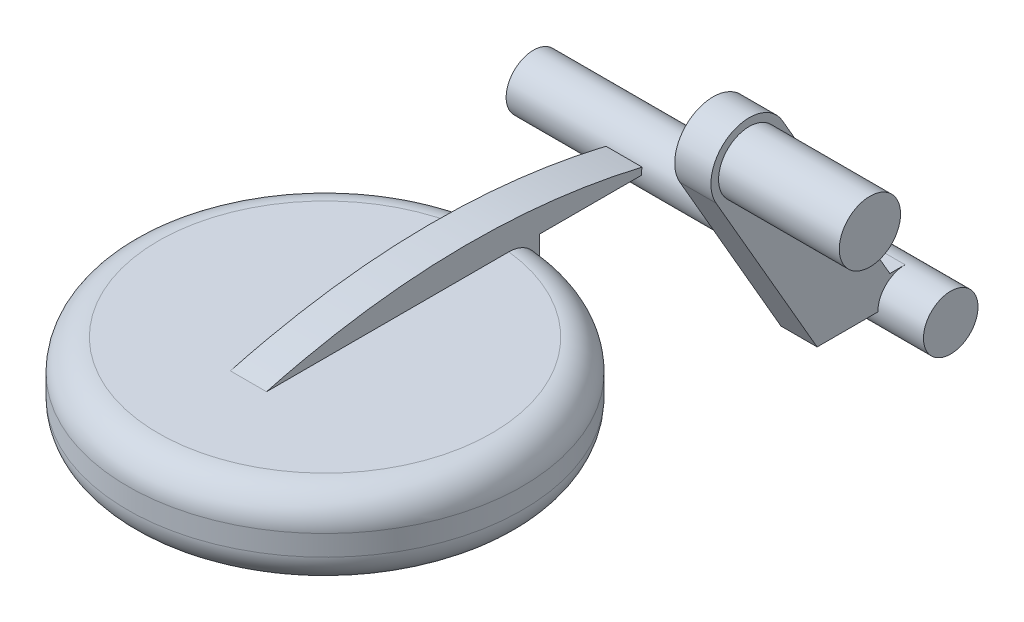
SolidWorks part; units mm, degrees
material "6061 Alloy"
ref_plane "Front Plane" through (0, 0, 0) normal (0, 0, 1) x (1, 0, 0)
ref_plane "Top Plane" through (0, 0, 0) normal (0, 1, 0) x (1, 0, 0)
ref_plane "Right Plane" through (0, 0, 0) normal (1, 0, 0) x (0, 0, -1)
sketch "Sketch1" plane through (0, 0, 0) normal (1, 0, 0) x (0, 0, -1)
  circle A0 centre (0, 0) radius 2.2606
  dimension "D1" = 4.5212
extrude "Boss-Extrude1" add sketch "Sketch1" along normal blind 34.5948
ref_plane "Plane1" through (8.2042, 0, 0) normal (1, 0, 0) x (0, 0, -1)
sketch "Sketch2" plane through (8.2042, 0, 0) normal (1, 0, 0) x (0, 0, -1)
  line L0 (0, 0) -> (-33.3248, 0)
  line L1 (2.4867, 0) -> (-2.4867, 0) construction
  spline S0 degree 2 poles (-33.3248, 0) (-16.5084, 4.5253) (0, 0) knots 0 0 0 1 1 1
  point P6 (0, 0)
  dimension "D1" = 33.3248
extrude "Boss-Extrude2" add sketch "Sketch2" along normal blind 2.9972
sketch "Sketch3" plane through (0, 0, 0) normal (0, -1, 0) x (1, 0, 0)
  line L0 (9.7028, 33.3248) -> (9.7028, 2.2606) construction
  line L1 (11.2014, 33.3248) -> (8.2042, 33.3248) construction
  line L2 (8.2042, 2.2606) -> (11.2014, 2.2606) construction
  circle A0 centre (9.7028, 26.9748) radius 16.3576
  dimension "D1" = 6.35
  dimension "D2" = 32.7152
extrude "Boss-Extrude3" add sketch "Sketch3" along normal blind 6.7818
fillet "Fillet1" radius 2.54 2 edges at (9.7028, 0, 43.3324) (9.7028, -6.7818, 10.6172)
ref_plane "Plane2" through (27.813, 0, 0) normal (1, 0, 0) x (0, 0, -1)
sketch "Sketch4" plane through (27.813, 0, 0) normal (1, 0, 0) x (0, 0, -1)
  line L0 (0, 0) -> (-7.2898, 0)
  line L1 (22.6873, 0) -> (-22.6873, 0) construction
  line L2 (-7.2898, 0) -> (-15.6718, 14.518)
  line L3 (-10.1725, 17.693) -> (-1.2626, 2.2606)
  line L4 (-1.2626, 2.2606) -> (0, 2.2606)
  line L5 (0, 6.0539) -> (0, -6.0539) construction
  line L6 (0, 2.2606) -> (0, 0)
  arc A0 (-15.6718, 14.518) -> (-10.1725, 17.693) centre (-12.9222, 16.1055) cw
  circle A1 centre (0, 0) radius 2.2606 construction
  point P8 (0, 0)
  point P15 (-12.2823, 10.5394)
  dimension "D1" = 60
  dimension "D2" = 7.2898
  dimension "D3" = 16.764
  dimension "D4" = 6.35
extrude "Boss-Extrude4" add sketch "Sketch4" along normal blind 2.9972
sketch "Sketch5" plane through (30.8102, 0, 0) normal (1, 0, 0) x (0, 0, -1)
  arc A0 (-10.1725, 17.693) -> (-15.6718, 14.518) centre (-12.9222, 16.1055) ccw construction
  arc A1 (-10.1725, 17.693) -> (-15.6718, 14.518) centre (-12.9222, 16.1055) ccw construction
  circle A2 centre (-12.9222, 16.1055) radius 2.54
  dimension "D1" = 5.08
extrude "Boss-Extrude5" add sketch "Sketch5" along normal blind 10.0076
